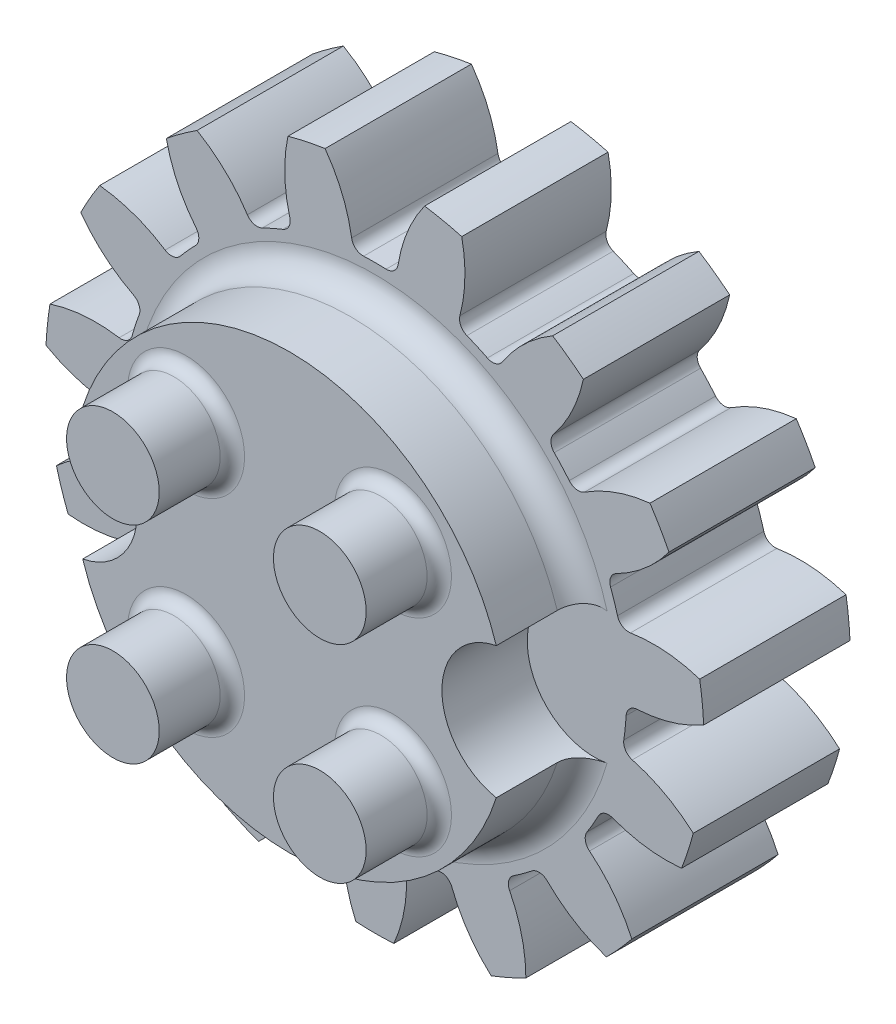
SolidWorks part; units mm, degrees
ref_plane "Front" through (0, 0, 0) normal (0, 0, 1) x (1, 0, 0)
ref_plane "Top" through (0, 0, 0) normal (0, 1, 0) x (1, 0, 0)
ref_plane "Right" through (0, 0, 0) normal (1, 0, 0) x (0, 0, -1)
sketch "Sketch1" plane through (0, 0, 0) normal (0, 0, 1) x (1, 0, 0)
  circle A0 centre (0, 0) radius 10.3235
  circle A1 centre (0, 0) radius 13.5
  circle A2 centre (0, 0) radius 11.9118
  dimension "D1" = 27
  dimension "D2" = 20.6471
  dimension "D3" = 23.8235
extrude "Boss-Extrude1" add sketch "Sketch1" along normal mid plane 6 contours A1
sketch "Sketch3" plane through (0, 0, 0) normal (0, 0, 1) x (1, 0, 0)
  line L0 (0, 0) -> (0, 13.5) construction
  line L1 (0, 0) -> (-0.8989, 10.2843) construction
  line L2 (-1.2451, 11.8465) -> (1.2451, 11.8465) construction
  line L3 (0, 8.4256) -> (-1.8029, 13.3791) construction
  line L4 (0, 0) -> (2.8068, 13.205) construction
  line L5 (1.2451, 11.8465) -> (3.6809, 11.3288) construction
  circle A7 centre (0, 0) radius 13.5 construction
  arc A10 (-2.0404, 13.3449) -> (-0.8989, 10.2843) centre (-7.003, 9.7508) cw
  arc A11 (2.0404, 13.3449) -> (0.8989, 10.2843) centre (7.003, 9.7508) ccw
  circle A12 centre (0, 0) radius 10.3235 construction
  arc A13 (-0.8989, 10.2843) -> (0.8989, 10.2843) centre (0, 0) cw
  arc A14 (-2.0404, 13.3449) -> (2.0404, 13.3449) centre (0, 0) cw
  circle A15 centre (0, 0) radius 11.9118 construction
  dimension "D1" = 20
  dimension "D2" = 12
extrude "Cut-Extrude1" cut sketch "Sketch3" against normal through all both and the other way through all
fillet "Fillet2" radius 0.4765 2 edges at (0.8989, 10.2843, 0) (-0.8989, 10.2843, 0)
pattern_circular "CirPattern1" count 15 over 360 about axis through (0, 0, 3) along (0, 0, -1) of "Cut-Extrude1", "Fillet2"
sketch "Sketch5" plane through (0, 0, 0) normal (0, 0, 1) x (1, 0, 0)
  circle A0 centre (0, 0) radius 1.25
  dimension "D1" = 2.5
extrude "Through_Center_Hole" cut sketch "Sketch5" against normal through all both and the other way through all
sketch "Sketch6" plane through (0, 0, 3) normal (0, 0, 1) x (1, 0, 0)
  line L0 (0, -9) -> (0, 9) construction
  line L1 (9, 0) -> (-9, 0) construction
  line L2 (-4.2426, -4.2426) -> (4.2426, 4.2426) construction
  line L3 (-4.2426, 4.2426) -> (4.2426, -4.2426) construction
  circle A0 centre (4.2426, 4.2426) radius 1.9 construction
  circle A1 centre (4.2426, -4.2426) radius 1.9 construction
  circle A2 centre (-4.2426, -4.2426) radius 1.9 construction
  circle A3 centre (-4.2426, 4.2426) radius 1.9 construction
  arc A4 (-8.4804, -2.7005) -> (-8.4804, 2.7005) centre (-9, 0) ccw
  arc A5 (8.4804, -2.7005) -> (8.4804, 2.7005) centre (9, 0) cw
  arc A6 (-8.4804, 2.7005) -> (8.4804, 2.7005) centre (0, 0) cw
  arc A7 (-8.4804, -2.7005) -> (8.4804, -2.7005) centre (0, 0) ccw
  dimension "D4" = 3.8
  dimension "D5" = 2.75
  dimension "D6" = 8.9
  dimension "D1" = 18
  dimension "D2" = 12
  dimension "D3" = 45
extrude "Boss-Extrude2" add sketch "Sketch6" along normal blind 3.5
sketch "Sketch7" plane through (0, 0, 6.5) normal (0, 0, 1) x (1, 0, 0)
  circle A0 centre (-4.2426, 4.2426) radius 1.9
  circle A1 centre (4.2426, 4.2426) radius 1.9
  circle A2 centre (4.2426, -4.2426) radius 1.9
  circle A3 centre (-4.2426, -4.2426) radius 1.9
  dimension "D1" = 3.8
extrude "Boss-Extrude3" add sketch "Sketch7" along normal blind 3
fillet "Fillet3" radius 1 2 edges at (0, -8.9, 3) (0, 8.9, 3)
fillet "Fillet4" radius 0.5 4 edges at (-2.3426, -4.2426, 6.5) (6.1426, -4.2426, 6.5) (6.1426, 4.2426, 6.5) (-2.3426, 4.2426, 6.5)
equation "\"od\"= 27'outside diameter"
equation "\"n\"= 15'number of teeth"
equation "\"m\"= \"od\" / ( \"n\" + 2 )'module"
equation "\"p\"= \"m\" * pi'pitch"
equation "\"d\"= \"m\" * \"n\"'primitive diameter"
equation "\"da\"= \"d\" + 2 * \"m\"'head diamater"
equation "\"df\"= \"d\" - 2 * \"m\"'foot diameter"
equation "\"D1@Sketch1\"=\"od\""
equation "\"D2@Sketch1\"=\"df\""
equation "\"D3@Sketch1\"=\"d\""
equation "\"D2@Sketch3\"=180/\"n\""
equation "\"D1@Fillet2\"=.3*\"m\""
equation "\"D1@CirPattern1\"=\"n\""
